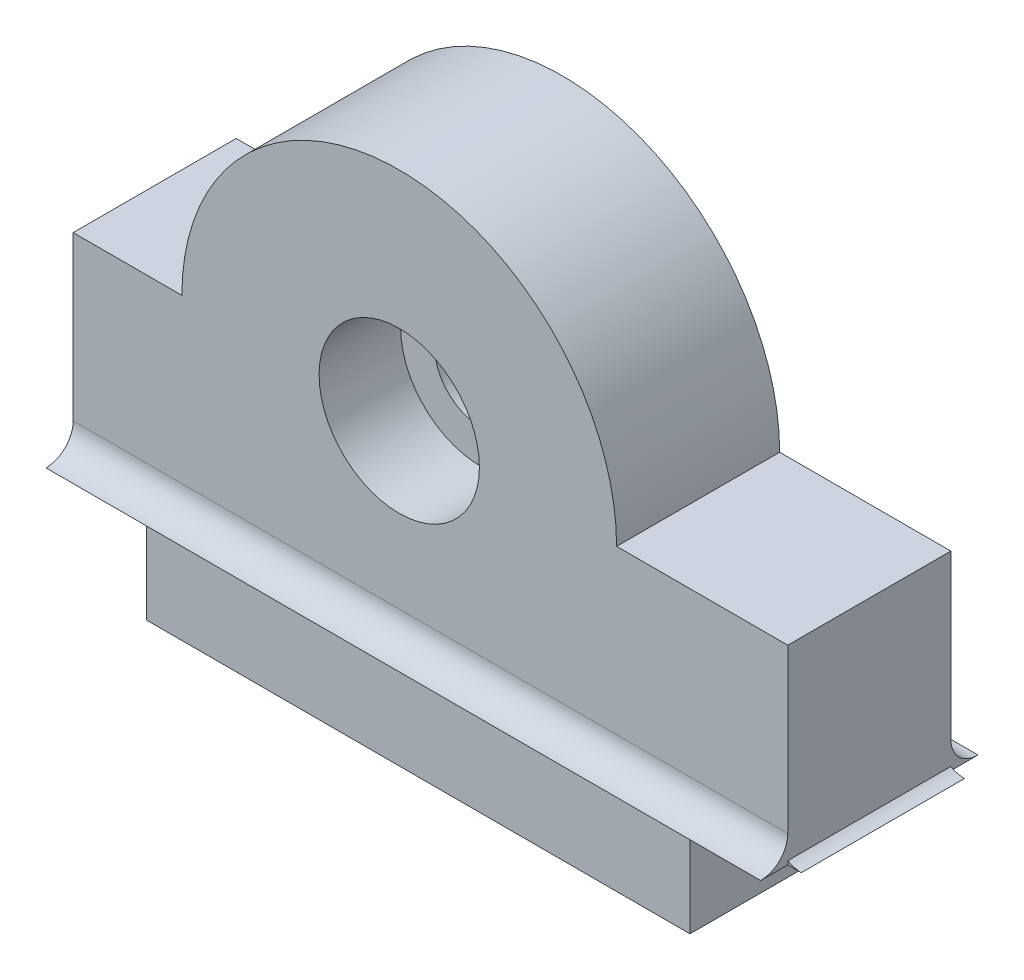
SolidWorks part; units mm, degrees
ref_plane "Front Plane" through (0, 0, 0) normal (0, 0, 1) x (1, 0, 0)
ref_plane "Top Plane" through (0, 0, 0) normal (0, 1, 0) x (1, 0, 0)
ref_plane "Right Plane" through (0, 0, 0) normal (1, 0, 0) x (0, 0, -1)
sketch "Sketch1" plane through (0, 0, 0) normal (0, 0, 1) x (1, 0, 0)
  line L0 (0, 0) -> (20, 0)
  line L1 (0, 0) -> (0, 4)
  line L2 (20, 0) -> (20, 4)
  line L3 (0, 4) -> (-2.7, 4)
  line L4 (23.6, 11) -> (23.6, 4)
  line L5 (-2.7, 4) -> (-2.7, 11)
  line L6 (-2.7, 11) -> (1.3, 11)
  line L7 (17.3, 11) -> (23.6, 11)
  line L8 (23.6, 4) -> (20, 4)
  line L9 (1.3, 11) -> (9.3, 11) construction
  line L10 (12.9373, 11) -> (9.3, 11) construction
  arc A0 (17.3, 11) -> (1.3, 11) centre (9.3, 11) ccw
  circle A1 centre (9.3, 11) radius 2.95
  point P19 (10, 0)
  point P22 (9.3, 11)
  dimension "D2" = 8
  dimension "D4" = 5.9
  dimension "D6" = 20
  dimension "D9" = 4
  dimension "D1" = 7
  dimension "D3" = 2.7
  dimension "D5" = 9.3
  dimension "D7" = 23.6
extrude "Boss-Extrude1" add sketch "Sketch1" along normal blind 6
sketch "Sketch2" plane through (-2.7, 0, 0) normal (-1, 0, 0) x (0, 0, 1)
  line L0 (3, 0) -> (3, 7) construction
  line L1 (6, 4) -> (6, 5)
  line L2 (6, 4) -> (7, 4)
  line L3 (0, 4) -> (-1, 4)
  line L4 (0, 4) -> (0, 5)
  arc A0 (6, 5) -> (7, 4) centre (7, 5) ccw
  arc A1 (0, 5) -> (-1, 4) centre (-1, 5) cw
  dimension "D1" = 1
  dimension "D2" = 1
  dimension "D3" = 6
  dimension "D4" = 3
  dimension "D5" = 4
extrude "Boss-Extrude2" add sketch "Sketch2" against normal up to surface (26.3 mm away) up to face at (23.6, 7.5, 3)
sketch "Sketch4" plane through (0, 0, 6) normal (0, 0, 1) x (1, 0, 0)
  line L0 (10.8, 0) -> (10.8, 7) construction
  line L1 (23.1, 4) -> (23.1, 5)
  line L2 (23.1, 4) -> (24.1, 4)
  line L3 (-1.5, 4) -> (-2.5, 4)
  line L4 (-1.5, 4) -> (-1.5, 5)
  arc A0 (23.1, 5) -> (24.1, 4) centre (24.1, 5) ccw
  arc A1 (-1.5, 5) -> (-2.5, 4) centre (-2.5, 5) cw
  dimension "D1" = 1
  dimension "D2" = 1
  dimension "D3" = 10.8
  dimension "D4" = 12.3
  dimension "D5" = 4
extrude "Boss-Extrude3" add sketch "Sketch4" against normal up to surface (6 mm away) up to face at (12.25, 11, 0)
sketch "Sketch5" plane through (0, 0, 0) normal (0, 0, -1) x (-1, 0, 0)
  line L0 (-9.3, 13.95) -> (-9.3, 8.05) construction
  circle A0 centre (-9.3, 11) radius 2.95 construction
  circle A1 centre (-9.3, 11) radius 1.7
  circle A2 centre (-9.3, 11) radius 2.95
  dimension "D1" = 3.4
  dimension "D2" = 5.9
extrude "Boss-Extrude4" add sketch "Sketch5" against normal blind 3
equation "\"D4@Sketch1\"= 5.5 + \"tol1@parametersSketch@prostheticParameters.SLDPRT\""
equation "\"D1@Sketch5\"= 3 + \"tol1@parametersSketch@prostheticParameters.SLDPRT\""
equation "\"D2@Sketch5\"= 5.5 + \"tol1@parametersSketch@prostheticParameters.SLDPRT\""
